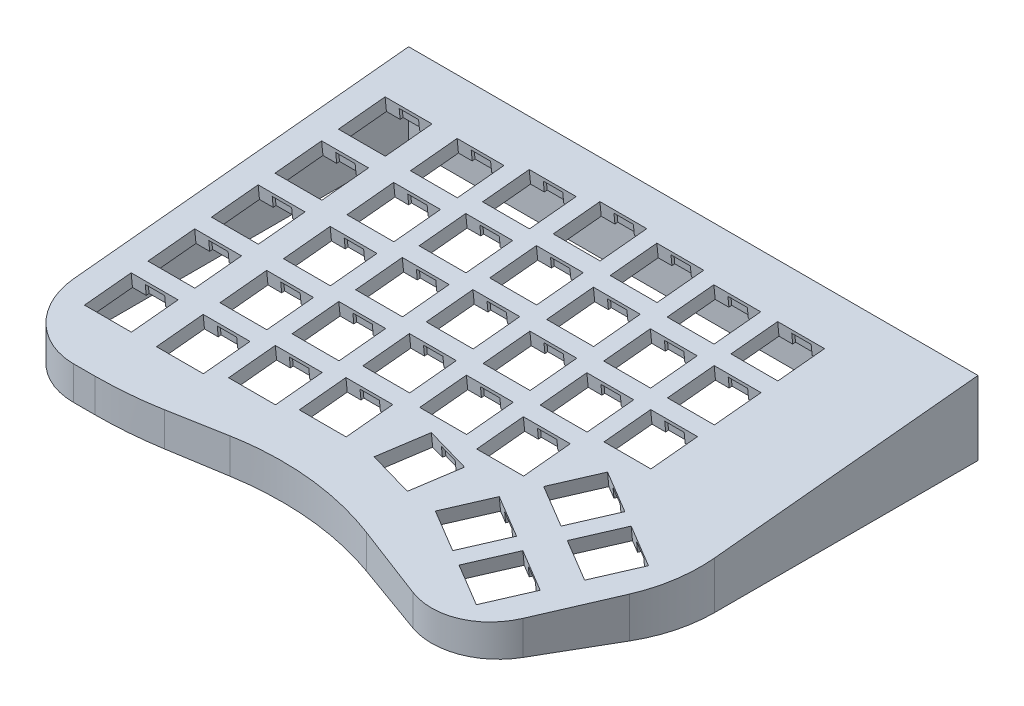
SolidWorks part; units mm, degrees
ref_plane "Front Plane" through (0, 0, 0) normal (0, 0, 1) x (1, 0, 0)
ref_plane "Top Plane" through (0, 0, 0) normal (0, 1, 0) x (1, 0, 0)
ref_plane "Right Plane" through (0, 0, 0) normal (1, 0, 0) x (0, 0, -1)
sketch "Key Template" plane through (0, 0, 0) normal (0, 1, 0) x (1, 0, 0)
  line L0 (41.2542, 10.7029) -> (27.2527, 10.7029)
  line L1 (27.2527, 10.7029) -> (27.2527, 9.7037)
  line L2 (27.2527, 9.7037) -> (26.4536, 9.7037)
  line L3 (26.4536, 9.7037) -> (26.4536, 6.6027)
  line L4 (26.4536, 6.6027) -> (27.2527, 6.6027)
  line L5 (27.2527, 6.6027) -> (27.2527, 0.8025)
  line L6 (27.2527, 0.8025) -> (26.4536, 0.8025)
  line L7 (26.4536, 0.8025) -> (26.4536, -2.2968)
  line L8 (26.4536, -2.2968) -> (27.2527, -2.2968)
  line L9 (27.2527, -2.2968) -> (27.2527, -3.2974)
  line L10 (27.2527, -3.2974) -> (41.2542, -3.2974)
  line L11 (41.2542, -3.2974) -> (41.2542, -2.2968)
  line L12 (41.2542, -2.2968) -> (42.0532, -2.2968)
  line L13 (42.0532, -2.2968) -> (42.0532, 0.8025)
  line L14 (42.0532, 0.8025) -> (41.2542, 0.8025)
  line L15 (41.2542, 0.8025) -> (41.2542, 6.6027)
  line L16 (41.2542, 6.6027) -> (42.0532, 6.6027)
  line L17 (42.0532, 6.6027) -> (42.0532, 9.7037)
  line L18 (42.0532, 9.7037) -> (41.2542, 9.7037)
  line L19 (41.2542, 9.7037) -> (41.2542, 10.7029)
  line L20 (41.2542, 29.7536) -> (27.2527, 29.7536)
  line L21 (27.2527, 29.7536) -> (27.2527, 28.7545)
  line L22 (27.2527, 28.7545) -> (26.4536, 28.7545)
  line L23 (26.4536, 28.7545) -> (26.4536, 25.6534)
  line L24 (26.4536, 25.6534) -> (27.2527, 25.6534)
  line L25 (27.2527, 25.6534) -> (27.2527, 19.8532)
  line L26 (27.2527, 19.8532) -> (26.4536, 19.8532)
  line L27 (26.4536, 19.8532) -> (26.4536, 16.7539)
  line L28 (26.4536, 16.7539) -> (27.2527, 16.7539)
  line L29 (27.2527, 16.7539) -> (27.2527, 15.7534)
  line L30 (27.2527, 15.7534) -> (41.2542, 15.7534)
  line L31 (41.2542, 15.7534) -> (41.2542, 16.7539)
  line L32 (41.2542, 16.7539) -> (42.0532, 16.7539)
  line L33 (42.0532, 16.7539) -> (42.0532, 19.8532)
  line L34 (42.0532, 19.8532) -> (41.2542, 19.8532)
  line L35 (41.2542, 19.8532) -> (41.2542, 25.6534)
  line L36 (41.2542, 25.6534) -> (42.0532, 25.6534)
  line L37 (42.0532, 25.6534) -> (42.0532, 28.7545)
  line L38 (42.0532, 28.7545) -> (41.2542, 28.7545)
  line L39 (41.2542, 28.7545) -> (41.2542, 29.7536)
  line L40 (27.2527, 53.8544) -> (41.2542, 53.8544)
  line L41 (41.2542, 53.8544) -> (41.2542, 54.8554)
  line L42 (41.2542, 54.8554) -> (42.0532, 54.8554)
  line L43 (42.0532, 54.8554) -> (42.0532, 57.9546)
  line L44 (42.0532, 57.9546) -> (41.2542, 57.9546)
  line L45 (41.2542, 57.9546) -> (41.2542, 63.7548)
  line L46 (41.2542, 63.7548) -> (42.0532, 63.7548)
  line L47 (42.0532, 63.7548) -> (42.0532, 66.8559)
  line L48 (42.0532, 66.8559) -> (41.2542, 66.8559)
  line L49 (41.2542, 66.8559) -> (41.2542, 67.8549)
  line L50 (41.2542, 67.8549) -> (27.2527, 67.8549)
  line L51 (27.2527, 67.8549) -> (27.2527, 66.8559)
  line L52 (27.2527, 66.8559) -> (26.4536, 66.8559)
  line L53 (26.4536, 66.8559) -> (26.4536, 63.7548)
  line L54 (26.4536, 63.7548) -> (27.2527, 63.7548)
  line L55 (27.2527, 63.7548) -> (27.2527, 57.9546)
  line L56 (27.2527, 57.9546) -> (26.4536, 57.9546)
  line L57 (26.4536, 57.9546) -> (26.4536, 54.8554)
  line L58 (26.4536, 54.8554) -> (27.2527, 54.8554)
  line L59 (27.2527, 54.8554) -> (27.2527, 53.8544)
  line L60 (27.2527, 34.8041) -> (41.2542, 34.8041)
  line L61 (41.2542, 34.8041) -> (41.2542, 35.8046)
  line L62 (41.2542, 35.8046) -> (42.0532, 35.8046)
  line L63 (42.0532, 35.8046) -> (42.0532, 38.9039)
  line L64 (42.0532, 38.9039) -> (41.2542, 38.9039)
  line L65 (41.2542, 38.9039) -> (41.2542, 44.7042)
  line L66 (41.2542, 44.7042) -> (42.0532, 44.7042)
  line L67 (42.0532, 44.7042) -> (42.0532, 47.8052)
  line L68 (42.0532, 47.8052) -> (41.2542, 47.8052)
  line L69 (41.2542, 47.8052) -> (41.2542, 48.8043)
  line L70 (41.2542, 48.8043) -> (27.2527, 48.8043)
  line L71 (27.2527, 48.8043) -> (27.2527, 47.8052)
  line L72 (27.2527, 47.8052) -> (26.4536, 47.8052)
  line L73 (26.4536, 47.8052) -> (26.4536, 44.7042)
  line L74 (26.4536, 44.7042) -> (27.2527, 44.7042)
  line L75 (27.2527, 44.7042) -> (27.2527, 38.9039)
  line L76 (27.2527, 38.9039) -> (26.4536, 38.9039)
  line L77 (26.4536, 38.9039) -> (26.4536, 35.8046)
  line L78 (26.4536, 35.8046) -> (27.2527, 35.8046)
  line L79 (27.2527, 35.8046) -> (27.2527, 34.8041)
  line L80 (46.3034, 44.3295) -> (60.3049, 44.3295)
  line L81 (60.3049, 44.3295) -> (60.3049, 45.33)
  line L82 (60.3049, 45.33) -> (61.1039, 45.33)
  line L83 (61.1039, 45.33) -> (61.1039, 48.4293)
  line L84 (61.1039, 48.4293) -> (60.3049, 48.4293)
  line L85 (60.3049, 48.4293) -> (60.3049, 54.2294)
  line L86 (60.3049, 54.2294) -> (61.1039, 54.2294)
  line L87 (61.1039, 54.2294) -> (61.1039, 57.3305)
  line L88 (61.1039, 57.3305) -> (60.3049, 57.3305)
  line L89 (60.3049, 57.3305) -> (60.3049, 58.3296)
  line L90 (60.3049, 58.3296) -> (46.3034, 58.3296)
  line L91 (46.3034, 58.3296) -> (46.3034, 57.3305)
  line L92 (46.3034, 57.3305) -> (45.5034, 57.3305)
  line L93 (45.5034, 57.3305) -> (45.5034, 54.2294)
  line L94 (45.5034, 54.2294) -> (46.3034, 54.2294)
  line L95 (46.3034, 54.2294) -> (46.3034, 48.4293)
  line L96 (46.3034, 48.4293) -> (45.5034, 48.4293)
  line L97 (45.5034, 48.4293) -> (45.5034, 45.33)
  line L98 (45.5034, 45.33) -> (46.3034, 45.33)
  line L99 (46.3034, 45.33) -> (46.3034, 44.3295)
  line L100 (60.3043, 34.5169) -> (46.304, 34.5169)
  line L101 (46.304, 34.5169) -> (46.304, 33.5169)
  line L102 (46.304, 33.5169) -> (45.505, 33.5169)
  line L103 (45.505, 33.5169) -> (45.505, 30.4158)
  line L104 (45.505, 30.4158) -> (46.304, 30.4158)
  line L105 (46.304, 30.4158) -> (46.304, 24.6166)
  line L106 (46.304, 24.6166) -> (45.505, 24.6166)
  line L107 (45.505, 24.6166) -> (45.505, 21.5164)
  line L108 (45.505, 21.5164) -> (46.304, 21.5164)
  line L109 (46.304, 21.5164) -> (46.304, 20.5154)
  line L110 (46.304, 20.5154) -> (60.3043, 20.5154)
  line L111 (60.3043, 20.5154) -> (60.3043, 21.5164)
  line L112 (60.3043, 21.5164) -> (61.1051, 21.5164)
  line L113 (61.1051, 21.5164) -> (61.1051, 24.6166)
  line L114 (61.1051, 24.6166) -> (60.3043, 24.6166)
  line L115 (60.3043, 24.6166) -> (60.3043, 30.4158)
  line L116 (60.3043, 30.4158) -> (61.1051, 30.4158)
  line L117 (61.1051, 30.4158) -> (61.1051, 33.5169)
  line L118 (61.1051, 33.5169) -> (60.3043, 33.5169)
  line L119 (60.3043, 33.5169) -> (60.3043, 34.5169)
  line L120 (63.726, -14.424) -> (75.8515, -21.4247)
  line L121 (75.8515, -21.4247) -> (76.3515, -20.5579)
  line L122 (76.3515, -20.5579) -> (77.0445, -20.9575)
  line L123 (77.0445, -20.9575) -> (78.5936, -18.273)
  line L124 (78.5936, -18.273) -> (77.9016, -17.8734)
  line L125 (77.9016, -17.8734) -> (80.8017, -12.8502)
  line L126 (80.8017, -12.8502) -> (81.4947, -13.2499)
  line L127 (81.4947, -13.2499) -> (83.0448, -10.5655)
  line L128 (83.0448, -10.5655) -> (82.3517, -10.1644)
  line L129 (82.3517, -10.1644) -> (82.8518, -9.299)
  line L130 (82.8518, -9.299) -> (70.7263, -2.2982)
  line L131 (70.7263, -2.2982) -> (70.2253, -3.165)
  line L132 (70.2253, -3.165) -> (69.5343, -2.7639)
  line L133 (69.5343, -2.7639) -> (67.9842, -5.45)
  line L134 (67.9842, -5.45) -> (68.6752, -5.8493)
  line L135 (68.6752, -5.8493) -> (65.7761, -10.8727)
  line L136 (65.7761, -10.8727) -> (65.0841, -10.4731)
  line L137 (65.0841, -10.4731) -> (63.534, -13.1574)
  line L138 (63.534, -13.1574) -> (64.2261, -13.5571)
  line L139 (64.2261, -13.5571) -> (63.726, -14.424)
  line L140 (58.8189, -22.9227) -> (51.8186, -35.0472)
  line L141 (51.8186, -35.0472) -> (52.6856, -35.546)
  line L142 (52.6856, -35.546) -> (52.2856, -36.2392)
  line L143 (52.2856, -36.2392) -> (54.9707, -37.7896)
  line L144 (54.9707, -37.7896) -> (55.3697, -37.0963)
  line L145 (55.3697, -37.0963) -> (60.3929, -39.9973)
  line L146 (60.3929, -39.9973) -> (59.9939, -40.6904)
  line L147 (59.9939, -40.6904) -> (62.678, -42.2394)
  line L148 (62.678, -42.2394) -> (63.079, -41.5462)
  line L149 (63.079, -41.5462) -> (63.9451, -42.0465)
  line L150 (63.9451, -42.0465) -> (70.9453, -29.9221)
  line L151 (70.9453, -29.9221) -> (70.0783, -29.4217)
  line L152 (70.0783, -29.4217) -> (70.4793, -28.73)
  line L153 (70.4793, -28.73) -> (67.7932, -27.1797)
  line L154 (67.7932, -27.1797) -> (67.3942, -27.8728)
  line L155 (67.3942, -27.8728) -> (62.371, -24.9719)
  line L156 (62.371, -24.9719) -> (62.771, -24.2787)
  line L157 (62.771, -24.2787) -> (60.0859, -22.7298)
  line L158 (60.0859, -22.7298) -> (59.6859, -23.4216)
  line L159 (59.6859, -23.4216) -> (58.8189, -22.9227)
  line L160 (42.3212, -13.3973) -> (35.32, -25.5218)
  line L161 (35.32, -25.5218) -> (36.187, -26.0206)
  line L162 (36.187, -26.0206) -> (35.786, -26.7138)
  line L163 (35.786, -26.7138) -> (38.4721, -28.2642)
  line L164 (38.4721, -28.2642) -> (38.8711, -27.571)
  line L165 (38.8711, -27.571) -> (43.8953, -30.4719)
  line L166 (43.8953, -30.4719) -> (43.4953, -31.165)
  line L167 (43.4953, -31.165) -> (46.1794, -32.7141)
  line L168 (46.1794, -32.7141) -> (46.5804, -32.0208)
  line L169 (46.5804, -32.0208) -> (47.4464, -32.5212)
  line L170 (47.4464, -32.5212) -> (54.4467, -20.3967)
  line L171 (54.4467, -20.3967) -> (53.5797, -19.8964)
  line L172 (53.5797, -19.8964) -> (53.9807, -19.2047)
  line L173 (53.9807, -19.2047) -> (51.2946, -17.6542)
  line L174 (51.2946, -17.6542) -> (50.8956, -18.3474)
  line L175 (50.8956, -18.3474) -> (45.8724, -15.4465)
  line L176 (45.8724, -15.4465) -> (46.2724, -14.7534)
  line L177 (46.2724, -14.7534) -> (43.5873, -13.2044)
  line L178 (43.5873, -13.2044) -> (43.1863, -13.8963)
  line L179 (43.1863, -13.8963) -> (42.3212, -13.3973)
  line L180 (47.2284, -4.8986) -> (59.3529, -11.8994)
  line L181 (59.3529, -11.8994) -> (59.8529, -11.0326)
  line L182 (59.8529, -11.0326) -> (60.5459, -11.4324)
  line L183 (60.5459, -11.4324) -> (62.095, -8.7476)
  line L184 (62.095, -8.7476) -> (61.402, -8.3478)
  line L185 (61.402, -8.3478) -> (64.3031, -3.3249)
  line L186 (64.3031, -3.3249) -> (64.9961, -3.7246)
  line L187 (64.9961, -3.7246) -> (66.5461, -1.0402)
  line L188 (66.5461, -1.0402) -> (65.8531, -0.6391)
  line L189 (65.8531, -0.6391) -> (66.3531, 0.2264)
  line L190 (66.3531, 0.2264) -> (54.2287, 7.2271)
  line L191 (54.2287, 7.2271) -> (53.7287, 6.3603)
  line L192 (53.7287, 6.3603) -> (53.0356, 6.7614)
  line L193 (53.0356, 6.7614) -> (51.4856, 4.0753)
  line L194 (51.4856, 4.0753) -> (52.1786, 3.676)
  line L195 (52.1786, 3.676) -> (49.2775, -1.3474)
  line L196 (49.2775, -1.3474) -> (48.5855, -0.9478)
  line L197 (48.5855, -0.9478) -> (47.0354, -3.6321)
  line L198 (47.0354, -3.6321) -> (47.7284, -4.0318)
  line L199 (47.7284, -4.0318) -> (47.2284, -4.8986)
  line L200 (-15.898, -5.9666) -> (-29.8992, -5.9666)
  line L201 (-29.8992, -5.9666) -> (-29.8992, -6.967)
  line L202 (-29.8992, -6.967) -> (-30.6986, -6.967)
  line L203 (-30.6986, -6.967) -> (-30.6986, -10.0667)
  line L204 (-30.6986, -10.0667) -> (-29.8992, -10.0667)
  line L205 (-29.8992, -10.0667) -> (-29.8992, -15.8668)
  line L206 (-29.8992, -15.8668) -> (-30.6986, -15.8668)
  line L207 (-30.6986, -15.8668) -> (-30.6986, -18.9675)
  line L208 (-30.6986, -18.9675) -> (-29.8992, -18.9675)
  line L209 (-29.8992, -18.9675) -> (-29.8992, -19.9667)
  line L210 (-29.8992, -19.9667) -> (-15.898, -19.9667)
  line L211 (-15.898, -19.9667) -> (-15.898, -18.9675)
  line L212 (-15.898, -18.9675) -> (-15.0985, -18.9675)
  line L213 (-15.0985, -18.9675) -> (-15.0985, -15.8668)
  line L214 (-15.0985, -15.8668) -> (-15.898, -15.8668)
  line L215 (-15.898, -15.8668) -> (-15.898, -10.0667)
  line L216 (-15.898, -10.0667) -> (-15.0985, -10.0667)
  line L217 (-15.0985, -10.0667) -> (-15.0985, -6.967)
  line L218 (-15.0985, -6.967) -> (-15.898, -6.967)
  line L219 (-15.898, -6.967) -> (-15.898, -5.9666)
  line L220 (3.1527, -3.5852) -> (-10.8485, -3.5852)
  line L221 (-10.8485, -3.5852) -> (-10.8485, -4.5857)
  line L222 (-10.8485, -4.5857) -> (-11.6479, -4.5857)
  line L223 (-11.6479, -4.5857) -> (-11.6479, -7.6853)
  line L224 (-11.6479, -7.6853) -> (-10.8485, -7.6853)
  line L225 (-10.8485, -7.6853) -> (-10.8485, -13.4855)
  line L226 (-10.8485, -13.4855) -> (-11.6479, -13.4855)
  line L227 (-11.6479, -13.4855) -> (-11.6479, -16.5863)
  line L228 (-11.6479, -16.5863) -> (-10.8485, -16.5863)
  line L229 (-10.8485, -16.5863) -> (-10.8485, -17.5854)
  line L230 (-10.8485, -17.5854) -> (3.1527, -17.5854)
  line L231 (3.1527, -17.5854) -> (3.1527, -16.5863)
  line L232 (3.1527, -16.5863) -> (3.9522, -16.5863)
  line L233 (3.9522, -16.5863) -> (3.9522, -13.4855)
  line L234 (3.9522, -13.4855) -> (3.1527, -13.4855)
  line L235 (3.1527, -13.4855) -> (3.1527, -7.6853)
  line L236 (3.1527, -7.6853) -> (3.9522, -7.6853)
  line L237 (3.9522, -7.6853) -> (3.9522, -4.5857)
  line L238 (3.9522, -4.5857) -> (3.1527, -4.5857)
  line L239 (3.1527, -4.5857) -> (3.1527, -3.5852)
  line L240 (3.1527, 15.4656) -> (-10.8485, 15.4656)
  line L241 (-10.8485, 15.4656) -> (-10.8485, 14.465)
  line L242 (-10.8485, 14.465) -> (-11.6479, 14.465)
  line L243 (-11.6479, 14.465) -> (-11.6479, 11.3654)
  line L244 (-11.6479, 11.3654) -> (-10.8485, 11.3654)
  line L245 (-10.8485, 11.3654) -> (-10.8485, 5.5652)
  line L246 (-10.8485, 5.5652) -> (-11.6479, 5.5652)
  line L247 (-11.6479, 5.5652) -> (-11.6479, 2.4645)
  line L248 (-11.6479, 2.4645) -> (-10.8485, 2.4645)
  line L249 (-10.8485, 2.4645) -> (-10.8485, 1.4653)
  line L250 (-10.8485, 1.4653) -> (3.1527, 1.4653)
  line L251 (3.1527, 1.4653) -> (3.1527, 2.4645)
  line L252 (3.1527, 2.4645) -> (3.9522, 2.4645)
  line L253 (3.9522, 2.4645) -> (3.9522, 5.5652)
  line L254 (3.9522, 5.5652) -> (3.1527, 5.5652)
  line L255 (3.1527, 5.5652) -> (3.1527, 11.3654)
  line L256 (3.1527, 11.3654) -> (3.9522, 11.3654)
  line L257 (3.9522, 11.3654) -> (3.9522, 14.465)
  line L258 (3.9522, 14.465) -> (3.1527, 14.465)
  line L259 (3.1527, 14.465) -> (3.1527, 15.4656)
  line L260 (-15.898, 13.0842) -> (-29.8992, 13.0842)
  line L261 (-29.8992, 13.0842) -> (-29.8992, 12.0837)
  line L262 (-29.8992, 12.0837) -> (-30.6986, 12.0837)
  line L263 (-30.6986, 12.0837) -> (-30.6986, 8.984)
  line L264 (-30.6986, 8.984) -> (-29.8992, 8.984)
  line L265 (-29.8992, 8.984) -> (-29.8992, 3.1838)
  line L266 (-29.8992, 3.1838) -> (-30.6986, 3.1838)
  line L267 (-30.6986, 3.1838) -> (-30.6986, 0.0832)
  line L268 (-30.6986, 0.0832) -> (-29.8992, 0.0832)
  line L269 (-29.8992, 0.0832) -> (-29.8992, -0.916)
  line L270 (-29.8992, -0.916) -> (-15.898, -0.916)
  line L271 (-15.898, -0.916) -> (-15.898, 0.0832)
  line L272 (-15.898, 0.0832) -> (-15.0985, 0.0832)
  line L273 (-15.0985, 0.0832) -> (-15.0985, 3.1838)
  line L274 (-15.0985, 3.1838) -> (-15.898, 3.1838)
  line L275 (-15.898, 3.1838) -> (-15.898, 8.984)
  line L276 (-15.898, 8.984) -> (-15.0985, 8.984)
  line L277 (-15.0985, 8.984) -> (-15.0985, 12.0837)
  line L278 (-15.0985, 12.0837) -> (-15.898, 12.0837)
  line L279 (-15.898, 12.0837) -> (-15.898, 13.0842)
  line L280 (-29.8992, 18.1348) -> (-15.898, 18.1348)
  line L281 (-15.898, 18.1348) -> (-15.898, 19.1339)
  line L282 (-15.898, 19.1339) -> (-15.0985, 19.1339)
  line L283 (-15.0985, 19.1339) -> (-15.0985, 22.2345)
  line L284 (-15.0985, 22.2345) -> (-15.898, 22.2345)
  line L285 (-15.898, 22.2345) -> (-15.898, 28.0347)
  line L286 (-15.898, 28.0347) -> (-15.0985, 28.0347)
  line L287 (-15.0985, 28.0347) -> (-15.0985, 31.1345)
  line L288 (-15.0985, 31.1345) -> (-15.898, 31.1345)
  line L289 (-15.898, 31.1345) -> (-15.898, 32.1349)
  line L290 (-15.898, 32.1349) -> (-29.8992, 32.1349)
  line L291 (-29.8992, 32.1349) -> (-29.8992, 31.1345)
  line L292 (-29.8992, 31.1345) -> (-30.6986, 31.1345)
  line L293 (-30.6986, 31.1345) -> (-30.6986, 28.0347)
  line L294 (-30.6986, 28.0347) -> (-29.8992, 28.0347)
  line L295 (-29.8992, 28.0347) -> (-29.8992, 22.2345)
  line L296 (-29.8992, 22.2345) -> (-30.6986, 22.2345)
  line L297 (-30.6986, 22.2345) -> (-30.6986, 19.1339)
  line L298 (-30.6986, 19.1339) -> (-29.8992, 19.1339)
  line L299 (-29.8992, 19.1339) -> (-29.8992, 18.1348)
  line L300 (-48.9499, 13.3721) -> (-34.9501, 13.3721)
  line L301 (-34.9501, 13.3721) -> (-34.9501, 14.3726)
  line L302 (-34.9501, 14.3726) -> (-34.1493, 14.3726)
  line L303 (-34.1493, 14.3726) -> (-34.1493, 17.4718)
  line L304 (-34.1493, 17.4718) -> (-34.9501, 17.4718)
  line L305 (-34.9501, 17.4718) -> (-34.9501, 23.2721)
  line L306 (-34.9501, 23.2721) -> (-34.1493, 23.2721)
  line L307 (-34.1493, 23.2721) -> (-34.1493, 26.3732)
  line L308 (-34.1493, 26.3732) -> (-34.9501, 26.3732)
  line L309 (-34.9501, 26.3732) -> (-34.9501, 27.3722)
  line L310 (-34.9501, 27.3722) -> (-48.9499, 27.3722)
  line L311 (-48.9499, 27.3722) -> (-48.9499, 26.3732)
  line L312 (-48.9499, 26.3732) -> (-49.7493, 26.3732)
  line L313 (-49.7493, 26.3732) -> (-49.7493, 23.2721)
  line L314 (-49.7493, 23.2721) -> (-48.9499, 23.2721)
  line L315 (-48.9499, 23.2721) -> (-48.9499, 17.4718)
  line L316 (-48.9499, 17.4718) -> (-49.7493, 17.4718)
  line L317 (-49.7493, 17.4718) -> (-49.7493, 14.3726)
  line L318 (-49.7493, 14.3726) -> (-48.9499, 14.3726)
  line L319 (-48.9499, 14.3726) -> (-48.9499, 13.3721)
  line L320 (-48.9499, -5.6786) -> (-34.9501, -5.6786)
  line L321 (-34.9501, -5.6786) -> (-34.9501, -4.6781)
  line L322 (-34.9501, -4.6781) -> (-34.1493, -4.6781)
  line L323 (-34.1493, -4.6781) -> (-34.1493, -1.5789)
  line L324 (-34.1493, -1.5789) -> (-34.9501, -1.5789)
  line L325 (-34.9501, -1.5789) -> (-34.9501, 4.2213)
  line L326 (-34.9501, 4.2213) -> (-34.1493, 4.2213)
  line L327 (-34.1493, 4.2213) -> (-34.1493, 7.3224)
  line L328 (-34.1493, 7.3224) -> (-34.9501, 7.3224)
  line L329 (-34.9501, 7.3224) -> (-34.9501, 8.3215)
  line L330 (-34.9501, 8.3215) -> (-48.9499, 8.3215)
  line L331 (-48.9499, 8.3215) -> (-48.9499, 7.3224)
  line L332 (-48.9499, 7.3224) -> (-49.7493, 7.3224)
  line L333 (-49.7493, 7.3224) -> (-49.7493, 4.2213)
  line L334 (-49.7493, 4.2213) -> (-48.9499, 4.2213)
  line L335 (-48.9499, 4.2213) -> (-48.9499, -1.5789)
  line L336 (-48.9499, -1.5789) -> (-49.7493, -1.5789)
  line L337 (-49.7493, -1.5789) -> (-49.7493, -4.6781)
  line L338 (-49.7493, -4.6781) -> (-48.9499, -4.6781)
  line L339 (-48.9499, -4.6781) -> (-48.9499, -5.6786)
  line L340 (-34.9487, -10.7292) -> (-48.9499, -10.7292)
  line L341 (-48.9499, -10.7292) -> (-48.9499, -11.7283)
  line L342 (-48.9499, -11.7283) -> (-49.7493, -11.7283)
  line L343 (-49.7493, -11.7283) -> (-49.7493, -14.8292)
  line L344 (-49.7493, -14.8292) -> (-48.9499, -14.8292)
  line L345 (-48.9499, -14.8292) -> (-48.9499, -20.6295)
  line L346 (-48.9499, -20.6295) -> (-49.7493, -20.6295)
  line L347 (-49.7493, -20.6295) -> (-49.7493, -23.7289)
  line L348 (-49.7493, -23.7289) -> (-48.9499, -23.7289)
  line L349 (-48.9499, -23.7289) -> (-48.9499, -24.7294)
  line L350 (-48.9499, -24.7294) -> (-34.9487, -24.7294)
  line L351 (-34.9487, -24.7294) -> (-34.9487, -23.7289)
  line L352 (-34.9487, -23.7289) -> (-34.1493, -23.7289)
  line L353 (-34.1493, -23.7289) -> (-34.1493, -20.6295)
  line L354 (-34.1493, -20.6295) -> (-34.9487, -20.6295)
  line L355 (-34.9487, -20.6295) -> (-34.9487, -14.8292)
  line L356 (-34.9487, -14.8292) -> (-34.1493, -14.8292)
  line L357 (-34.1493, -14.8292) -> (-34.1493, -11.7283)
  line L358 (-34.1493, -11.7283) -> (-34.9487, -11.7283)
  line L359 (-34.9487, -11.7283) -> (-34.9487, -10.7292)
  line L360 (-53.9993, -10.7292) -> (-68.0006, -10.7292)
  line L361 (-68.0006, -10.7292) -> (-68.0006, -11.7283)
  line L362 (-68.0006, -11.7283) -> (-68.8, -11.7283)
  line L363 (-68.8, -11.7283) -> (-68.8, -14.8292)
  line L364 (-68.8, -14.8292) -> (-68.0006, -14.8292)
  line L365 (-68.0006, -14.8292) -> (-68.0006, -20.6295)
  line L366 (-68.0006, -20.6295) -> (-68.8, -20.6295)
  line L367 (-68.8, -20.6295) -> (-68.8, -23.7289)
  line L368 (-68.8, -23.7289) -> (-68.0006, -23.7289)
  line L369 (-68.0006, -23.7289) -> (-68.0006, -24.7294)
  line L370 (-68.0006, -24.7294) -> (-53.9993, -24.7294)
  line L371 (-53.9993, -24.7294) -> (-53.9993, -23.7289)
  line L372 (-53.9993, -23.7289) -> (-53.2, -23.7289)
  line L373 (-53.2, -23.7289) -> (-53.2, -20.6295)
  line L374 (-53.2, -20.6295) -> (-53.9993, -20.6295)
  line L375 (-53.9993, -20.6295) -> (-53.9993, -14.8292)
  line L376 (-53.9993, -14.8292) -> (-53.2, -14.8292)
  line L377 (-53.2, -14.8292) -> (-53.2, -11.7283)
  line L378 (-53.2, -11.7283) -> (-53.9993, -11.7283)
  line L379 (-53.9993, -11.7283) -> (-53.9993, -10.7292)
  line L380 (-56.382, 8.3215) -> (-70.382, 8.3215)
  line L381 (-70.382, 8.3215) -> (-70.382, 7.3224)
  line L382 (-70.382, 7.3224) -> (-71.1827, 7.3224)
  line L383 (-71.1827, 7.3224) -> (-71.1827, 4.2213)
  line L384 (-71.1827, 4.2213) -> (-70.382, 4.2213)
  line L385 (-70.382, 4.2213) -> (-70.382, -1.5789)
  line L386 (-70.382, -1.5789) -> (-71.1827, -1.5789)
  line L387 (-71.1827, -1.5789) -> (-71.1827, -4.6781)
  line L388 (-71.1827, -4.6781) -> (-70.382, -4.6781)
  line L389 (-70.382, -4.6781) -> (-70.382, -5.6786)
  line L390 (-70.382, -5.6786) -> (-56.382, -5.6786)
  line L391 (-56.382, -5.6786) -> (-56.382, -4.6781)
  line L392 (-56.382, -4.6781) -> (-55.5813, -4.6781)
  line L393 (-55.5813, -4.6781) -> (-55.5813, -1.5789)
  line L394 (-55.5813, -1.5789) -> (-56.382, -1.5789)
  line L395 (-56.382, -1.5789) -> (-56.382, 4.2213)
  line L396 (-56.382, 4.2213) -> (-55.5813, 4.2213)
  line L397 (-55.5813, 4.2213) -> (-55.5813, 7.3224)
  line L398 (-55.5813, 7.3224) -> (-56.382, 7.3224)
  line L399 (-56.382, 7.3224) -> (-56.382, 8.3215)
  line L400 (-56.382, 27.3722) -> (-70.382, 27.3722)
  line L401 (-70.382, 27.3722) -> (-70.382, 26.3732)
  line L402 (-70.382, 26.3732) -> (-71.1827, 26.3732)
  line L403 (-71.1827, 26.3732) -> (-71.1827, 23.2721)
  line L404 (-71.1827, 23.2721) -> (-70.382, 23.2721)
  line L405 (-70.382, 23.2721) -> (-70.382, 17.4718)
  line L406 (-70.382, 17.4718) -> (-71.1827, 17.4718)
  line L407 (-71.1827, 17.4718) -> (-71.1827, 14.3726)
  line L408 (-71.1827, 14.3726) -> (-70.382, 14.3726)
  line L409 (-70.382, 14.3726) -> (-70.382, 13.3721)
  line L410 (-70.382, 13.3721) -> (-56.382, 13.3721)
  line L411 (-56.382, 13.3721) -> (-56.382, 14.3726)
  line L412 (-56.382, 14.3726) -> (-55.5813, 14.3726)
  line L413 (-55.5813, 14.3726) -> (-55.5813, 17.4718)
  line L414 (-55.5813, 17.4718) -> (-56.382, 17.4718)
  line L415 (-56.382, 17.4718) -> (-56.382, 23.2721)
  line L416 (-56.382, 23.2721) -> (-55.5813, 23.2721)
  line L417 (-55.5813, 23.2721) -> (-55.5813, 26.3732)
  line L418 (-55.5813, 26.3732) -> (-56.382, 26.3732)
  line L419 (-56.382, 26.3732) -> (-56.382, 27.3722)
  line L420 (3.1527, 34.5163) -> (-10.8485, 34.5163)
  line L421 (-10.8485, 34.5163) -> (-10.8485, 33.5157)
  line L422 (-10.8485, 33.5157) -> (-11.6479, 33.5157)
  line L423 (-11.6479, 33.5157) -> (-11.6479, 30.4161)
  line L424 (-11.6479, 30.4161) -> (-10.8485, 30.4161)
  line L425 (-10.8485, 30.4161) -> (-10.8485, 24.6159)
  line L426 (-10.8485, 24.6159) -> (-11.6479, 24.6159)
  line L427 (-11.6479, 24.6159) -> (-11.6479, 21.5152)
  line L428 (-11.6479, 21.5152) -> (-10.8485, 21.5152)
  line L429 (-10.8485, 21.5152) -> (-10.8485, 20.516)
  line L430 (-10.8485, 20.516) -> (3.1527, 20.516)
  line L431 (3.1527, 20.516) -> (3.1527, 21.5152)
  line L432 (3.1527, 21.5152) -> (3.9522, 21.5152)
  line L433 (3.9522, 21.5152) -> (3.9522, 24.6159)
  line L434 (3.9522, 24.6159) -> (3.1527, 24.6159)
  line L435 (3.1527, 24.6159) -> (3.1527, 30.4161)
  line L436 (3.1527, 30.4161) -> (3.9522, 30.4161)
  line L437 (3.9522, 30.4161) -> (3.9522, 33.5157)
  line L438 (3.9522, 33.5157) -> (3.1527, 33.5157)
  line L439 (3.1527, 33.5157) -> (3.1527, 34.5163)
  line L440 (3.1527, 53.5674) -> (-10.8485, 53.5674)
  line L441 (-10.8485, 53.5674) -> (-10.8485, 52.5664)
  line L442 (-10.8485, 52.5664) -> (-11.6479, 52.5664)
  line L443 (-11.6479, 52.5664) -> (-11.6479, 49.4668)
  line L444 (-11.6479, 49.4668) -> (-10.8485, 49.4668)
  line L445 (-10.8485, 49.4668) -> (-10.8485, 43.6666)
  line L446 (-10.8485, 43.6666) -> (-11.6479, 43.6666)
  line L447 (-11.6479, 43.6666) -> (-11.6479, 40.5659)
  line L448 (-11.6479, 40.5659) -> (-10.8485, 40.5659)
  line L449 (-10.8485, 40.5659) -> (-10.8485, 39.5668)
  line L450 (-10.8485, 39.5668) -> (3.1527, 39.5668)
  line L451 (3.1527, 39.5668) -> (3.1527, 40.5659)
  line L452 (3.1527, 40.5659) -> (3.9522, 40.5659)
  line L453 (3.9522, 40.5659) -> (3.9522, 43.6666)
  line L454 (3.9522, 43.6666) -> (3.1527, 43.6666)
  line L455 (3.1527, 43.6666) -> (3.1527, 49.4668)
  line L456 (3.1527, 49.4668) -> (3.9522, 49.4668)
  line L457 (3.9522, 49.4668) -> (3.9522, 52.5664)
  line L458 (3.9522, 52.5664) -> (3.1527, 52.5664)
  line L459 (3.1527, 52.5664) -> (3.1527, 53.5674)
  line L460 (-15.898, 51.1853) -> (-29.8992, 51.1853)
  line L461 (-29.8992, 51.1853) -> (-29.8992, 50.1852)
  line L462 (-29.8992, 50.1852) -> (-30.6986, 50.1852)
  line L463 (-30.6986, 50.1852) -> (-30.6986, 47.0856)
  line L464 (-30.6986, 47.0856) -> (-29.8992, 47.0856)
  line L465 (-29.8992, 47.0856) -> (-29.8992, 41.2852)
  line L466 (-29.8992, 41.2852) -> (-30.6986, 41.2852)
  line L467 (-30.6986, 41.2852) -> (-30.6986, 38.1846)
  line L468 (-30.6986, 38.1846) -> (-29.8992, 38.1846)
  line L469 (-29.8992, 38.1846) -> (-29.8992, 37.1855)
  line L470 (-29.8992, 37.1855) -> (-15.898, 37.1855)
  line L471 (-15.898, 37.1855) -> (-15.898, 38.1846)
  line L472 (-15.898, 38.1846) -> (-15.0985, 38.1846)
  line L473 (-15.0985, 38.1846) -> (-15.0985, 41.2852)
  line L474 (-15.0985, 41.2852) -> (-15.898, 41.2852)
  line L475 (-15.898, 41.2852) -> (-15.898, 47.0856)
  line L476 (-15.898, 47.0856) -> (-15.0985, 47.0856)
  line L477 (-15.0985, 47.0856) -> (-15.0985, 50.1852)
  line L478 (-15.0985, 50.1852) -> (-15.898, 50.1852)
  line L479 (-15.898, 50.1852) -> (-15.898, 51.1853)
  line L480 (-34.9501, 46.4229) -> (-48.9499, 46.4229)
  line L481 (-48.9499, 46.4229) -> (-48.9499, 45.4239)
  line L482 (-48.9499, 45.4239) -> (-49.7493, 45.4239)
  line L483 (-49.7493, 45.4239) -> (-49.7493, 42.3229)
  line L484 (-49.7493, 42.3229) -> (-48.9499, 42.3229)
  line L485 (-48.9499, 42.3229) -> (-48.9499, 36.5226)
  line L486 (-48.9499, 36.5226) -> (-49.7493, 36.5226)
  line L487 (-49.7493, 36.5226) -> (-49.7493, 33.4233)
  line L488 (-49.7493, 33.4233) -> (-48.9499, 33.4233)
  line L489 (-48.9499, 33.4233) -> (-48.9499, 32.4228)
  line L490 (-48.9499, 32.4228) -> (-34.9501, 32.4228)
  line L491 (-34.9501, 32.4228) -> (-34.9501, 33.4233)
  line L492 (-34.9501, 33.4233) -> (-34.1493, 33.4233)
  line L493 (-34.1493, 33.4233) -> (-34.1493, 36.5226)
  line L494 (-34.1493, 36.5226) -> (-34.9501, 36.5226)
  line L495 (-34.9501, 36.5226) -> (-34.9501, 42.3229)
  line L496 (-34.9501, 42.3229) -> (-34.1493, 42.3229)
  line L497 (-34.1493, 42.3229) -> (-34.1493, 45.4239)
  line L498 (-34.1493, 45.4239) -> (-34.9501, 45.4239)
  line L499 (-34.9501, 45.4239) -> (-34.9501, 46.4229)
  line L500 (-70.382, 51.4733) -> (-56.3813, 51.4733)
  line L501 (-56.3813, 51.4733) -> (-56.3813, 52.4744)
  line L502 (-56.3813, 52.4744) -> (-55.5813, 52.4744)
  line L503 (-55.5813, 52.4744) -> (-55.5813, 55.5744)
  line L504 (-55.5813, 55.5744) -> (-56.3813, 55.5744)
  line L505 (-56.3813, 55.5744) -> (-56.3813, 61.3744)
  line L506 (-56.3813, 61.3744) -> (-55.5813, 61.3744)
  line L507 (-55.5813, 61.3744) -> (-55.5813, 64.4744)
  line L508 (-55.5813, 64.4744) -> (-56.382, 64.4744)
  line L509 (-56.382, 64.4744) -> (-56.382, 65.4744)
  line L510 (-56.382, 65.4744) -> (-70.382, 65.4744)
  line L511 (-70.382, 65.4744) -> (-70.382, 64.4744)
  line L512 (-70.382, 64.4744) -> (-71.182, 64.4744)
  line L513 (-71.182, 64.4744) -> (-71.182, 61.3744)
  line L514 (-71.182, 61.3744) -> (-70.382, 61.3744)
  line L515 (-70.382, 61.3744) -> (-70.382, 55.5744)
  line L516 (-70.382, 55.5744) -> (-71.1827, 55.5744)
  line L517 (-71.1827, 55.5744) -> (-71.1827, 52.4744)
  line L518 (-71.1827, 52.4744) -> (-70.382, 52.4744)
  line L519 (-70.382, 52.4744) -> (-70.382, 51.4733)
  line L520 (-48.9499, 51.4733) -> (-34.9501, 51.4733)
  line L521 (-34.9501, 51.4733) -> (-34.9501, 52.4744)
  line L522 (-34.9501, 52.4744) -> (-34.1493, 52.4744)
  line L523 (-34.1493, 52.4744) -> (-34.1493, 55.5735)
  line L524 (-34.1493, 55.5735) -> (-34.9501, 55.5735)
  line L525 (-34.9501, 55.5735) -> (-34.9501, 61.3737)
  line L526 (-34.9501, 61.3737) -> (-34.1493, 61.3737)
  line L527 (-34.1493, 61.3737) -> (-34.1493, 64.4748)
  line L528 (-34.1493, 64.4748) -> (-34.9501, 64.4748)
  line L529 (-34.9501, 64.4748) -> (-34.9501, 65.4739)
  line L530 (-34.9501, 65.4739) -> (-48.9499, 65.4739)
  line L531 (-48.9499, 65.4739) -> (-48.9499, 64.4748)
  line L532 (-48.9499, 64.4748) -> (-49.7493, 64.4748)
  line L533 (-49.7493, 64.4748) -> (-49.7493, 61.3737)
  line L534 (-49.7493, 61.3737) -> (-48.9499, 61.3737)
  line L535 (-48.9499, 61.3737) -> (-48.9499, 55.5735)
  line L536 (-48.9499, 55.5735) -> (-49.7493, 55.5735)
  line L537 (-49.7493, 55.5735) -> (-49.7493, 52.4744)
  line L538 (-49.7493, 52.4744) -> (-48.9499, 52.4744)
  line L539 (-48.9499, 52.4744) -> (-48.9499, 51.4733)
  line L540 (-29.8992, 56.2365) -> (-15.898, 56.2365)
  line L541 (-15.898, 56.2365) -> (-15.898, 57.2355)
  line L542 (-15.898, 57.2355) -> (-15.0985, 57.2355)
  line L543 (-15.0985, 57.2355) -> (-15.0985, 60.3357)
  line L544 (-15.0985, 60.3357) -> (-15.898, 60.3357)
  line L545 (-15.898, 60.3357) -> (-15.898, 66.1359)
  line L546 (-15.898, 66.1359) -> (-15.0985, 66.1359)
  line L547 (-15.0985, 66.1359) -> (-15.0985, 69.236)
  line L548 (-15.0985, 69.236) -> (-15.898, 69.236)
  line L549 (-15.898, 69.236) -> (-15.898, 70.236)
  line L550 (-15.898, 70.236) -> (-29.8992, 70.236)
  line L551 (-29.8992, 70.236) -> (-29.8992, 69.236)
  line L552 (-29.8992, 69.236) -> (-30.6986, 69.236)
  line L553 (-30.6986, 69.236) -> (-30.6986, 66.1359)
  line L554 (-30.6986, 66.1359) -> (-29.8992, 66.1359)
  line L555 (-29.8992, 66.1359) -> (-29.8992, 60.3357)
  line L556 (-29.8992, 60.3357) -> (-30.6986, 60.3357)
  line L557 (-30.6986, 60.3357) -> (-30.6986, 57.2355)
  line L558 (-30.6986, 57.2355) -> (-29.8992, 57.2355)
  line L559 (-29.8992, 57.2355) -> (-29.8992, 56.2365)
  line L560 (-10.8485, 58.6176) -> (3.1527, 58.6176)
  line L561 (3.1527, 58.6176) -> (3.1527, 59.6166)
  line L562 (3.1527, 59.6166) -> (3.9522, 59.6166)
  line L563 (3.9522, 59.6166) -> (3.9522, 62.7177)
  line L564 (3.9522, 62.7177) -> (3.1527, 62.7177)
  line L565 (3.1527, 62.7177) -> (3.1527, 68.518)
  line L566 (3.1527, 68.518) -> (3.9522, 68.518)
  line L567 (3.9522, 68.518) -> (3.9522, 71.6171)
  line L568 (3.9522, 71.6171) -> (3.1527, 71.6171)
  line L569 (3.1527, 71.6171) -> (3.1527, 72.6181)
  line L570 (3.1527, 72.6181) -> (-10.8485, 72.6181)
  line L571 (-10.8485, 72.6181) -> (-10.8485, 71.6171)
  line L572 (-10.8485, 71.6171) -> (-11.6479, 71.6171)
  line L573 (-11.6479, 71.6171) -> (-11.6479, 68.518)
  line L574 (-11.6479, 68.518) -> (-10.8485, 68.518)
  line L575 (-10.8485, 68.518) -> (-10.8485, 62.7177)
  line L576 (-10.8485, 62.7177) -> (-11.6479, 62.7177)
  line L577 (-11.6479, 62.7177) -> (-11.6479, 59.6166)
  line L578 (-11.6479, 59.6166) -> (-10.8485, 59.6166)
  line L579 (-10.8485, 59.6166) -> (-10.8485, 58.6176)
  line L580 (8.2022, 56.2365) -> (22.2035, 56.2365)
  line L581 (22.2035, 56.2365) -> (22.2035, 57.2355)
  line L582 (22.2035, 57.2355) -> (23.0025, 57.2355)
  line L583 (23.0025, 57.2355) -> (23.0025, 60.3357)
  line L584 (23.0025, 60.3357) -> (22.2035, 60.3357)
  line L585 (22.2035, 60.3357) -> (22.2035, 66.1359)
  line L586 (22.2035, 66.1359) -> (23.0025, 66.1359)
  line L587 (23.0025, 66.1359) -> (23.0025, 69.236)
  line L588 (23.0025, 69.236) -> (22.2035, 69.236)
  line L589 (22.2035, 69.236) -> (22.2035, 70.236)
  line L590 (22.2035, 70.236) -> (8.2022, 70.236)
  line L591 (8.2022, 70.236) -> (8.2022, 69.236)
  line L592 (8.2022, 69.236) -> (7.4028, 69.236)
  line L593 (7.4028, 69.236) -> (7.4028, 66.1359)
  line L594 (7.4028, 66.1359) -> (8.2022, 66.1359)
  line L595 (8.2022, 66.1359) -> (8.2022, 60.3357)
  line L596 (8.2022, 60.3357) -> (7.4028, 60.3357)
  line L597 (7.4028, 60.3357) -> (7.4028, 57.2355)
  line L598 (7.4028, 57.2355) -> (8.2022, 57.2355)
  line L599 (8.2022, 57.2355) -> (8.2022, 56.2365)
  line L600 (8.2022, 37.1855) -> (22.2035, 37.1855)
  line L601 (22.2035, 37.1855) -> (22.2035, 38.1846)
  line L602 (22.2035, 38.1846) -> (23.0025, 38.1846)
  line L603 (23.0025, 38.1846) -> (23.0025, 41.2852)
  line L604 (23.0025, 41.2852) -> (22.2035, 41.2852)
  line L605 (22.2035, 41.2852) -> (22.2035, 47.0856)
  line L606 (22.2035, 47.0856) -> (23.0025, 47.0856)
  line L607 (23.0025, 47.0856) -> (23.0025, 50.1852)
  line L608 (23.0025, 50.1852) -> (22.2035, 50.1852)
  line L609 (22.2035, 50.1852) -> (22.2035, 51.1853)
  line L610 (22.2035, 51.1853) -> (8.2022, 51.1853)
  line L611 (8.2022, 51.1853) -> (8.2022, 50.1852)
  line L612 (8.2022, 50.1852) -> (7.4028, 50.1852)
  line L613 (7.4028, 50.1852) -> (7.4028, 47.0856)
  line L614 (7.4028, 47.0856) -> (8.2022, 47.0856)
  line L615 (8.2022, 47.0856) -> (8.2022, 41.2852)
  line L616 (8.2022, 41.2852) -> (7.4028, 41.2852)
  line L617 (7.4028, 41.2852) -> (7.4028, 38.1846)
  line L618 (7.4028, 38.1846) -> (8.2022, 38.1846)
  line L619 (8.2022, 38.1846) -> (8.2022, 37.1855)
  line L620 (22.2035, 13.0842) -> (8.2022, 13.0842)
  line L621 (8.2022, 13.0842) -> (8.2022, 12.0837)
  line L622 (8.2022, 12.0837) -> (7.4028, 12.0837)
  line L623 (7.4028, 12.0837) -> (7.4028, 8.984)
  line L624 (7.4028, 8.984) -> (8.2022, 8.984)
  line L625 (8.2022, 8.984) -> (8.2022, 3.1838)
  line L626 (8.2022, 3.1838) -> (7.4028, 3.1838)
  line L627 (7.4028, 3.1838) -> (7.4028, 0.0832)
  line L628 (7.4028, 0.0832) -> (8.2022, 0.0832)
  line L629 (8.2022, 0.0832) -> (8.2022, -0.916)
  line L630 (8.2022, -0.916) -> (22.2035, -0.916)
  line L631 (22.2035, -0.916) -> (22.2035, 0.0832)
  line L632 (22.2035, 0.0832) -> (23.0025, 0.0832)
  line L633 (23.0025, 0.0832) -> (23.0025, 3.1838)
  line L634 (23.0025, 3.1838) -> (22.2035, 3.1838)
  line L635 (22.2035, 3.1838) -> (22.2035, 8.984)
  line L636 (22.2035, 8.984) -> (23.0025, 8.984)
  line L637 (23.0025, 8.984) -> (23.0025, 12.0837)
  line L638 (23.0025, 12.0837) -> (22.2035, 12.0837)
  line L639 (22.2035, 12.0837) -> (22.2035, 13.0842)
  line L640 (8.2022, 18.1348) -> (22.2035, 18.1348)
  line L641 (22.2035, 18.1348) -> (22.2035, 19.1339)
  line L642 (22.2035, 19.1339) -> (23.0025, 19.1339)
  line L643 (23.0025, 19.1339) -> (23.0025, 22.2345)
  line L644 (23.0025, 22.2345) -> (22.2035, 22.2345)
  line L645 (22.2035, 22.2345) -> (22.2035, 28.0347)
  line L646 (22.2035, 28.0347) -> (23.0025, 28.0347)
  line L647 (23.0025, 28.0347) -> (23.0025, 31.1345)
  line L648 (23.0025, 31.1345) -> (22.2035, 31.1345)
  line L649 (22.2035, 31.1345) -> (22.2035, 32.1349)
  line L650 (22.2035, 32.1349) -> (8.2022, 32.1349)
  line L651 (8.2022, 32.1349) -> (8.2022, 31.1345)
  line L652 (8.2022, 31.1345) -> (7.4028, 31.1345)
  line L653 (7.4028, 31.1345) -> (7.4028, 28.0347)
  line L654 (7.4028, 28.0347) -> (8.2022, 28.0347)
  line L655 (8.2022, 28.0347) -> (8.2022, 22.2345)
  line L656 (8.2022, 22.2345) -> (7.4028, 22.2345)
  line L657 (7.4028, 22.2345) -> (7.4028, 19.1339)
  line L658 (7.4028, 19.1339) -> (8.2022, 19.1339)
  line L659 (8.2022, 19.1339) -> (8.2022, 18.1348)
  line L660 (12.6605, -21.0457) -> (26.1846, -24.6688)
  line L661 (26.1846, -24.6688) -> (26.4436, -23.7027)
  line L662 (26.4436, -23.7027) -> (27.2157, -23.9108)
  line L663 (27.2157, -23.9108) -> (28.0177, -20.9148)
  line L664 (28.0177, -20.9148) -> (27.2457, -20.7081)
  line L665 (27.2457, -20.7081) -> (28.7467, -15.1062)
  line L666 (28.7467, -15.1062) -> (29.5197, -15.3129)
  line L667 (29.5197, -15.3129) -> (30.3218, -12.3182)
  line L668 (30.3218, -12.3182) -> (29.5487, -12.1115)
  line L669 (29.5487, -12.1115) -> (29.8078, -11.1454)
  line L670 (29.8078, -11.1454) -> (16.2832, -7.5213)
  line L671 (16.2832, -7.5213) -> (16.0257, -8.4872)
  line L672 (16.0257, -8.4872) -> (15.2524, -8.2804)
  line L673 (15.2524, -8.2804) -> (14.4506, -11.275)
  line L674 (14.4506, -11.275) -> (15.2235, -11.4817)
  line L675 (15.2235, -11.4817) -> (13.7213, -17.0851)
  line L676 (13.7213, -17.0851) -> (12.9483, -16.8784)
  line L677 (12.9483, -16.8784) -> (12.1465, -19.8716)
  line L678 (12.1465, -19.8716) -> (12.9194, -20.0797)
  line L679 (12.9194, -20.0797) -> (12.6605, -21.0457)
  line L680 (-56.382, 46.4229) -> (-70.382, 46.4229)
  line L681 (-70.382, 46.4229) -> (-70.382, 45.4239)
  line L682 (-70.382, 45.4239) -> (-71.1827, 45.4239)
  line L683 (-71.1827, 45.4239) -> (-71.1827, 42.3229)
  line L684 (-71.1827, 42.3229) -> (-70.382, 42.3229)
  line L685 (-70.382, 42.3229) -> (-70.382, 36.5226)
  line L686 (-70.382, 36.5226) -> (-71.1827, 36.5226)
  line L687 (-71.1827, 36.5226) -> (-71.1827, 33.4233)
  line L688 (-71.1827, 33.4233) -> (-70.382, 33.4233)
  line L689 (-70.382, 33.4233) -> (-70.382, 32.4228)
  line L690 (-70.382, 32.4228) -> (-56.382, 32.4228)
  line L691 (-56.382, 32.4228) -> (-56.382, 33.4233)
  line L692 (-56.382, 33.4233) -> (-55.5813, 33.4233)
  line L693 (-55.5813, 33.4233) -> (-55.5813, 36.5226)
  line L694 (-55.5813, 36.5226) -> (-56.382, 36.5226)
  line L695 (-56.382, 36.5226) -> (-56.382, 42.3229)
  line L696 (-56.382, 42.3229) -> (-55.5813, 42.3229)
  line L697 (-55.5813, 42.3229) -> (-55.5813, 45.4239)
  line L698 (-55.5813, 45.4239) -> (-56.382, 45.4239)
  line L699 (-56.382, 45.4239) -> (-56.382, 46.4229)
  point P0 (51.2946, -17.6542)
  point P1 (22.2035, 8.984)
  point P2 (26.1846, -24.6688)
  point P3 (-70.382, 45.4239)
  dimension "D5" = 0.8
sketch "BodySketch" plane through (0, 0, 0) normal (0, 1, 0) x (1, 0, 0)
  line L0 (-78.182, 78.6181) -> (91.818, 78.6181)
  line L1 (91.818, 78.6181) -> (91.818, -10.7704)
  line L3 (91.818, -10.7704) -> (66.4624, -54.6862)
  line L4 (66.4624, -54.6862) -> (7.1738, -33.3819)
  line L5 (7.1738, -33.3819) -> (-42.182, -41.3819)
  line L6 (-42.182, -41.3819) -> (-78.182, -41.3819)
  line L7 (-78.182, -41.3819) -> (-78.182, 78.6181)
  line L9 (63.9451, -42.0465) -> (70.9453, -29.9221) construction
  dimension "D1" = 170
  dimension "D2" = 120
  dimension "D3" = 36
  dimension "D4" = 50
  dimension "D5" = 63
  dimension "D9" = 112
sketch3d "3DSketch2"
  line L0 (-42.182, 0, 41.3819) -> (-42.182, 10, 41.3819)
  line L1 (-35.1103, 0, -78.6181) -> (-35.1103, 22, -78.6181)
  line L2 (-78.182, 0, -78.6181) -> (91.818, 0, -78.6181) construction
  line L3 (52.292, 0, -78.6181) -> (52.292, 22, -78.6181)
  dimension "D1" = 10
  dimension "D2" = 22
  dimension "D3" = 22
ref_plane "Plane2" through (0, 13.9982, 1.3998) normal (0, 0.995, 0.0995) x (1, 0, 0)
extrude "Boss-Extrude1" add sketch "BodySketch" along normal up to surface (10 mm away) up to plane "Plane2"
sketch "Sketch9" plane through (0, 13.9982, 1.3998) normal (0, 0.995, 0.0995) x (1, 0, 0)
  line L0 (-70.226, 65.3696) -> (-56.226, 65.3696)
  line L1 (-56.226, 65.3696) -> (-56.226, 51.3696)
  line L2 (-56.226, 51.3696) -> (-70.226, 51.3696)
  line L3 (-70.226, 51.3696) -> (-70.226, 65.3696)
  line L6 (-70.226, 32.3196) -> (-70.226, 46.3196)
  line L7 (-70.226, 46.3196) -> (-56.226, 46.3196)
  line L8 (-56.226, 46.3196) -> (-56.226, 32.3196)
  line L9 (-56.226, 32.3196) -> (-70.226, 32.3196)
  line L10 (-70.226, 13.2696) -> (-70.226, 27.2696)
  line L11 (-70.226, 27.2696) -> (-56.226, 27.2696)
  line L12 (-56.226, 27.2696) -> (-56.226, 13.2696)
  line L13 (-56.226, 13.2696) -> (-70.226, 13.2696)
  line L14 (-70.226, -5.7804) -> (-70.226, 8.2196)
  line L15 (-70.226, 8.2196) -> (-56.226, 8.2196)
  line L16 (-56.226, 8.2196) -> (-56.226, -5.7804)
  line L17 (-56.226, -5.7804) -> (-70.226, -5.7804)
  line L18 (-48.726, 51.3696) -> (-48.726, 65.3696)
  line L19 (-48.726, 65.3696) -> (-34.726, 65.3696)
  line L20 (-34.726, 65.3696) -> (-34.726, 51.3696)
  line L21 (-34.726, 51.3696) -> (-48.726, 51.3696)
  line L22 (-48.726, 32.3196) -> (-48.726, 46.3196)
  line L23 (-48.726, 46.3196) -> (-34.726, 46.3196)
  line L24 (-34.726, 46.3196) -> (-34.726, 32.3196)
  line L25 (-34.726, 32.3196) -> (-48.726, 32.3196)
  line L26 (-48.726, 13.2696) -> (-48.726, 27.2696)
  line L27 (-48.726, 27.2696) -> (-34.726, 27.2696)
  line L28 (-34.726, 27.2696) -> (-34.726, 13.2696)
  line L29 (-34.726, 13.2696) -> (-48.726, 13.2696)
  line L30 (-48.726, -5.7804) -> (-48.726, 8.2196)
  line L31 (-48.726, 8.2196) -> (-34.726, 8.2196)
  line L32 (-34.726, 8.2196) -> (-34.726, -5.7804)
  line L33 (-34.726, -5.7804) -> (-48.726, -5.7804)
  line L34 (-29.676, 53.8696) -> (-29.676, 67.8696)
  line L35 (-15.676, 67.8696) -> (-15.676, 53.8696)
  line L36 (-15.676, 34.8196) -> (-29.676, 34.8196)
  line L37 (-29.676, 29.7696) -> (-15.676, 29.7696)
  line L38 (-15.676, 29.7696) -> (-15.676, 15.7696)
  line L39 (-29.676, 67.8696) -> (-15.676, 67.8696)
  line L40 (-15.676, 48.8196) -> (-15.676, 34.8196)
  line L41 (-15.676, 53.8696) -> (-29.676, 53.8696)
  line L42 (-29.676, 10.7196) -> (-15.676, 10.7196)
  line L43 (-29.676, 48.8196) -> (-15.676, 48.8196)
  line L44 (-15.676, 15.7696) -> (-29.676, 15.7696)
  line L45 (-29.676, -3.2804) -> (-29.676, 10.7196)
  line L46 (-29.676, 34.8196) -> (-29.676, 48.8196)
  line L47 (-15.676, 10.7196) -> (-15.676, -3.2804)
  line L48 (-29.676, 15.7696) -> (-29.676, 29.7696)
  line L49 (-15.676, -3.2804) -> (-29.676, -3.2804)
  line L50 (-10.626, 12.7696) -> (3.374, 12.7696)
  line L51 (3.374, 50.8696) -> (3.374, 36.8696)
  line L52 (3.374, 36.8696) -> (-10.626, 36.8696)
  line L53 (3.374, -1.2304) -> (-10.626, -1.2304)
  line L54 (-10.626, 50.8696) -> (3.374, 50.8696)
  line L55 (-10.626, -1.2304) -> (-10.626, 12.7696)
  line L56 (3.374, 55.9196) -> (-10.626, 55.9196)
  line L57 (-10.626, 36.8696) -> (-10.626, 50.8696)
  line L58 (3.374, 12.7696) -> (3.374, -1.2304)
  line L59 (3.374, 17.8196) -> (-10.626, 17.8196)
  line L60 (-10.626, 31.8196) -> (3.374, 31.8196)
  line L61 (-10.626, 55.9196) -> (-10.626, 69.9196)
  line L62 (3.374, 69.9196) -> (3.374, 55.9196)
  line L63 (-10.626, 17.8196) -> (-10.626, 31.8196)
  line L64 (3.374, 31.8196) -> (3.374, 17.8196)
  line L65 (-10.626, 69.9196) -> (3.374, 69.9196)
  line L66 (22.424, 29.7696) -> (22.424, 15.7696)
  line L67 (22.424, 10.7196) -> (22.424, -3.2804)
  line L68 (8.424, 53.8696) -> (8.424, 67.8696)
  line L69 (8.424, 34.8196) -> (8.424, 48.8196)
  line L70 (8.424, 67.8696) -> (22.424, 67.8696)
  line L71 (22.424, 15.7696) -> (8.424, 15.7696)
  line L72 (22.424, 67.8696) -> (22.424, 53.8696)
  line L73 (8.424, 10.7196) -> (22.424, 10.7196)
  line L74 (22.424, 48.8196) -> (22.424, 34.8196)
  line L75 (8.424, -3.2804) -> (8.424, 10.7196)
  line L76 (22.424, -3.2804) -> (8.424, -3.2804)
  line L77 (8.424, 15.7696) -> (8.424, 29.7696)
  line L78 (22.424, 34.8196) -> (8.424, 34.8196)
  line L79 (8.424, 48.8196) -> (22.424, 48.8196)
  line L80 (8.424, 29.7696) -> (22.424, 29.7696)
  line L81 (22.424, 53.8696) -> (8.424, 53.8696)
  line L82 (27.474, 8.6696) -> (41.474, 8.6696)
  line L83 (41.474, 65.8196) -> (41.474, 51.8196)
  line L84 (27.474, 27.7196) -> (41.474, 27.7196)
  line L85 (41.474, 51.8196) -> (27.474, 51.8196)
  line L86 (27.474, 46.7696) -> (41.474, 46.7696)
  line L87 (27.474, 32.7696) -> (27.474, 46.7696)
  line L88 (27.474, 65.8196) -> (41.474, 65.8196)
  line L89 (27.474, -5.3304) -> (27.474, 8.6696)
  line L90 (27.474, 51.8196) -> (27.474, 65.8196)
  line L91 (41.474, 8.6696) -> (41.474, -5.3304)
  line L92 (41.474, 13.7196) -> (27.474, 13.7196)
  line L93 (41.474, -5.3304) -> (27.474, -5.3304)
  line L94 (41.474, 27.7196) -> (41.474, 13.7196)
  line L95 (41.474, 32.7696) -> (27.474, 32.7696)
  line L96 (27.474, 13.7196) -> (27.474, 27.7196)
  line L97 (41.474, 46.7696) -> (41.474, 32.7696)
  line L98 (60.524, 27.7196) -> (60.524, 13.7196)
  line L99 (46.524, 32.7696) -> (46.524, 46.7696)
  line L100 (60.524, 32.7696) -> (46.524, 32.7696)
  line L101 (46.524, 46.7696) -> (60.524, 46.7696)
  line L102 (60.524, 46.7696) -> (60.524, 32.7696)
  line L103 (60.524, 65.8196) -> (60.524, 51.8196)
  line L104 (46.524, 51.8196) -> (46.524, 65.8196)
  line L105 (46.524, 27.7196) -> (60.524, 27.7196)
  line L106 (46.524, 13.7196) -> (46.524, 27.7196)
  line L107 (46.524, 65.8196) -> (60.524, 65.8196)
  line L108 (60.524, 13.7196) -> (46.524, 13.7196)
  line L109 (60.524, 51.8196) -> (46.524, 51.8196)
  line L110 (-10.626, -6.2804) -> (3.374, -6.2804)
  line L111 (-70.226, -24.8304) -> (-70.226, -10.8304)
  line L112 (-34.726, -24.8304) -> (-48.726, -24.8304)
  line L113 (-15.676, -8.3304) -> (-15.676, -22.3304)
  line L114 (-15.676, -22.3304) -> (-29.676, -22.3304)
  line L115 (-34.726, -10.8304) -> (-34.726, -24.8304)
  line L116 (3.374, -6.2804) -> (3.374, -20.2804)
  line L117 (-70.226, -10.8304) -> (-56.226, -10.8304)
  line L118 (-48.726, -24.8304) -> (-48.726, -10.8304)
  line L119 (-48.726, -10.8304) -> (-34.726, -10.8304)
  line L120 (3.374, -20.2804) -> (-10.626, -20.2804)
  line L121 (-29.676, -8.3304) -> (-15.676, -8.3304)
  line L122 (-10.626, -20.2804) -> (-10.626, -6.2804)
  line L123 (-56.226, -10.8304) -> (-56.226, -24.8304)
  line L124 (-56.226, -24.8304) -> (-70.226, -24.8304)
  line L125 (-29.676, -22.3304) -> (-29.676, -8.3304)
  line L126 (54.4508, -20.4908) -> (47.4551, -32.6176)
  line L127 (42.3239, -13.4951) -> (54.4508, -20.4908)
  line L128 (35.3283, -25.622) -> (42.3239, -13.4951)
  line L129 (47.4551, -32.6176) -> (35.3283, -25.622)
  line L130 (63.7456, -14.5993) -> (70.7413, -2.4724)
  line L132 (71.0016, -30.0385) -> (64.006, -42.1654)
  line L133 (58.8748, -23.0428) -> (71.0016, -30.0385)
  line L134 (51.8791, -35.1697) -> (58.8748, -23.0428)
  line L135 (64.006, -42.1654) -> (51.8791, -35.1697)
  line L136 (82.8681, -9.468) -> (75.8725, -21.5949)
  line L137 (54.1904, 7.0753) -> (66.3173, 0.0797)
  line L138 (70.7413, -2.4724) -> (82.8681, -9.468)
  line L139 (59.3216, -12.0472) -> (47.1948, -5.0516)
  line L140 (75.8725, -21.5949) -> (63.7456, -14.5993)
  line L141 (66.3173, 0.0797) -> (59.3216, -12.0472)
  line L142 (47.1948, -5.0516) -> (54.1904, 7.0753)
  line L143 (16.221, -7.6353) -> (29.7439, -11.259)
  line L144 (12.5973, -21.1582) -> (16.221, -7.6353)
  line L145 (29.7439, -11.259) -> (26.1202, -24.7819)
  line L146 (26.1202, -24.7819) -> (12.5973, -21.1582)
  dimension "D1" = 14
  dimension "D2" = 14
  dimension "D6" = 5.05
  dimension "D8" = 7.5
  dimension "D10" = 5.05
  dimension "D11" = 14
  dimension "D12" = 14
  dimension "D13" = 14
  dimension "D14" = 14
  dimension "D16" = 14
  dimension "D17" = 14
  dimension "D20" = 14
  dimension "D21" = 14
  dimension "D22" = 7.5
  dimension "D5" = 4
  dimension "D7" = 2
  dimension "D9" = 4
fillet "Fillet1" radius 20 1 edges at (-78.182, 5, 41.3819)
fillet "Fillet2" radius 120 1 edges at (-42.182, 5, 41.3819)
fillet "Fillet3" radius 90 1 edges at (7.1738, 5.4, 33.3819)
fillet "Fillet4" radius 20 1 edges at (66.4624, 4.3348, 54.6862)
fillet "Fillet5" radius 40 1 edges at (91.818, 6.5306, 10.7704)
sketch "Sketch10" plane through (0, 0, 0) normal (0, -1, 0) x (1, 0, 0)
  line L14 (87.818, -74.6181) -> (87.818, 0.0521)
  line L15 (82.9946, 18.0526) -> (71.3545, 38.2132)
  line L16 (52.0876, 45.2704) -> (30.4087, 37.4805)
  line L17 (-16.4186, 33.1537) -> (-33.2842, 35.8875)
  line L18 (-51.8442, 37.3819) -> (-58.182, 37.3819)
  line L19 (-74.182, 21.3819) -> (-74.182, -74.6181)
  line L20 (-74.182, -74.6181) -> (87.818, -74.6181)
  line L21 (87.818, -74.6181) -> (87.818, 0.0521)
  line L22 (82.9946, 18.0526) -> (71.3545, 38.2132)
  line L23 (52.0876, 45.2704) -> (30.4087, 37.4805)
  line L24 (-16.4186, 33.1537) -> (-33.2842, 35.8875)
  line L25 (-51.8442, 37.3819) -> (-58.182, 37.3819)
  line L26 (-74.182, 21.3819) -> (-74.182, -74.6181)
  line L27 (-74.182, -74.6181) -> (87.818, -74.6181)
  arc A10 (87.818, 0.0521) -> (82.9946, 18.0526) centre (51.818, 0.0521) ccw
  arc A11 (71.3545, 38.2132) -> (52.0876, 45.2704) centre (57.4982, 30.213) ccw
  arc A12 (-16.4186, 33.1537) -> (30.4087, 37.4805) centre (-1.3786, 125.9427) ccw
  arc A13 (-33.2842, 35.8875) -> (-51.8442, 37.3819) centre (-51.8442, -78.6181) ccw
  arc A14 (-58.182, 37.3819) -> (-74.182, 21.3819) centre (-58.182, 21.3819) ccw
  arc A15 (87.818, 0.0521) -> (82.9946, 18.0526) centre (51.818, 0.0521) ccw
  arc A16 (71.3545, 38.2132) -> (52.0876, 45.2704) centre (57.4982, 30.213) ccw
  arc A17 (-16.4186, 33.1537) -> (30.4087, 37.4805) centre (-1.3786, 125.9427) ccw
  arc A18 (-33.2842, 35.8875) -> (-51.8442, 37.3819) centre (-51.8442, -78.6181) ccw
  arc A19 (-58.182, 37.3819) -> (-74.182, 21.3819) centre (-58.182, 21.3819) ccw
  dimension "D1" = 4
extrude "Cut-Extrude1" cut sketch "Sketch10" against normal offset from surface (7.98 mm away) 4 up to face at (9.08, 12.6311, 15.0705)
extrude "Cut-Extrude2" cut sketch "Sketch9" against normal through all
sketch "Sketch11" plane through (0, 10.0181, 1.0018) normal (0, -0.995, -0.0995) x (1, 0, 0)
  line L0 (-56.226, 24.8304) -> (-56.226, 10.8304) construction
  line L1 (-66.126, 25.6804) -> (-60.326, 25.6804)
  line L2 (-66.126, 25.6804) -> (-66.126, 9.9804)
  line L3 (-66.126, 9.9804) -> (-60.326, 9.9804)
  line L4 (-60.326, 25.6804) -> (-60.326, 9.9804)
  line L5 (-66.126, 25.6804) -> (-60.326, 9.9804) construction
  line L6 (-66.126, 9.9804) -> (-60.326, 25.6804) construction
  line L7 (-70.226, 10.8304) -> (-70.226, 24.8304) construction
  line L8 (-70.226, 24.8304) -> (-56.226, 24.8304) construction
  line L9 (-56.226, 10.8304) -> (-70.226, 10.8304) construction
  line L10 (-44.626, 25.6804) -> (-44.626, 9.9804)
  line L11 (-44.626, 9.9804) -> (-38.826, 9.9804)
  line L12 (-44.626, 25.6804) -> (-38.826, 9.9804) construction
  line L13 (-38.826, 25.6804) -> (-38.826, 9.9804)
  line L14 (-44.626, 9.9804) -> (-38.826, 25.6804) construction
  line L15 (-44.626, 25.6804) -> (-38.826, 25.6804)
  line L16 (-25.576, 23.1804) -> (-25.576, 7.4804)
  line L17 (-25.576, 7.4804) -> (-19.776, 7.4804)
  line L18 (-25.576, 23.1804) -> (-19.776, 7.4804) construction
  line L19 (-19.776, 23.1804) -> (-19.776, 7.4804)
  line L20 (-25.576, 7.4804) -> (-19.776, 23.1804) construction
  line L21 (-25.576, 23.1804) -> (-19.776, 23.1804)
  line L22 (-6.526, 21.1304) -> (-6.526, 5.4304)
  line L23 (-6.526, 5.4304) -> (-0.726, 5.4304)
  line L24 (-6.526, 21.1304) -> (-0.726, 5.4304) construction
  line L25 (-0.726, 21.1304) -> (-0.726, 5.4304)
  line L26 (-6.526, 5.4304) -> (-0.726, 21.1304) construction
  line L27 (-6.526, 21.1304) -> (-0.726, 21.1304)
  line L28 (-6.526, 2.0804) -> (-6.526, -13.6196)
  line L29 (-6.526, -13.6196) -> (-0.726, -13.6196)
  line L30 (-6.526, 2.0804) -> (-0.726, -13.6196) construction
  line L31 (-0.726, 2.0804) -> (-0.726, -13.6196)
  line L32 (-6.526, -13.6196) -> (-0.726, 2.0804) construction
  line L33 (-6.526, 2.0804) -> (-0.726, 2.0804)
  line L34 (-25.576, 4.1304) -> (-25.576, -11.5696)
  line L35 (-25.576, -11.5696) -> (-19.776, -11.5696)
  line L36 (-25.576, 4.1304) -> (-19.776, -11.5696) construction
  line L37 (-19.776, 4.1304) -> (-19.776, -11.5696)
  line L38 (-25.576, -11.5696) -> (-19.776, 4.1304) construction
  line L39 (-25.576, 4.1304) -> (-19.776, 4.1304)
  line L40 (-44.626, 6.6304) -> (-44.626, -9.0696)
  line L41 (-44.626, -9.0696) -> (-38.826, -9.0696)
  line L42 (-44.626, 6.6304) -> (-38.826, -9.0696) construction
  line L43 (-38.826, 6.6304) -> (-38.826, -9.0696)
  line L44 (-44.626, -9.0696) -> (-38.826, 6.6304) construction
  line L45 (-44.626, 6.6304) -> (-38.826, 6.6304)
  line L46 (-66.126, 6.6304) -> (-66.126, -9.0696)
  line L47 (-66.126, -9.0696) -> (-60.326, -9.0696)
  line L48 (-66.126, 6.6304) -> (-60.326, -9.0696) construction
  line L49 (-60.326, 6.6304) -> (-60.326, -9.0696)
  line L50 (-66.126, -9.0696) -> (-60.326, 6.6304) construction
  line L51 (-66.126, 6.6304) -> (-60.326, 6.6304)
  line L52 (-66.126, -12.4196) -> (-66.126, -28.1196)
  line L53 (-66.126, -28.1196) -> (-60.326, -28.1196)
  line L54 (-66.126, -12.4196) -> (-60.326, -28.1196) construction
  line L55 (-60.326, -12.4196) -> (-60.326, -28.1196)
  line L56 (-66.126, -28.1196) -> (-60.326, -12.4196) construction
  line L57 (-66.126, -12.4196) -> (-60.326, -12.4196)
  line L58 (-44.626, -12.4196) -> (-44.626, -28.1196)
  line L59 (-44.626, -28.1196) -> (-38.826, -28.1196)
  line L60 (-44.626, -12.4196) -> (-38.826, -28.1196) construction
  line L61 (-38.826, -12.4196) -> (-38.826, -28.1196)
  line L62 (-44.626, -28.1196) -> (-38.826, -12.4196) construction
  line L63 (-44.626, -12.4196) -> (-38.826, -12.4196)
  line L64 (-25.576, -14.9196) -> (-25.576, -30.6196)
  line L65 (-25.576, -30.6196) -> (-19.776, -30.6196)
  line L66 (-25.576, -14.9196) -> (-19.776, -30.6196) construction
  line L67 (-19.776, -14.9196) -> (-19.776, -30.6196)
  line L68 (-25.576, -30.6196) -> (-19.776, -14.9196) construction
  line L69 (-25.576, -14.9196) -> (-19.776, -14.9196)
  line L70 (-6.526, -16.9696) -> (-6.526, -32.6696)
  line L71 (-6.526, -32.6696) -> (-0.726, -32.6696)
  line L72 (-6.526, -16.9696) -> (-0.726, -32.6696) construction
  line L73 (-0.726, -16.9696) -> (-0.726, -32.6696)
  line L74 (-6.526, -32.6696) -> (-0.726, -16.9696) construction
  line L75 (-6.526, -16.9696) -> (-0.726, -16.9696)
  line L76 (-6.526, -36.0196) -> (-6.526, -51.7196)
  line L77 (-6.526, -51.7196) -> (-0.726, -51.7196)
  line L78 (-6.526, -36.0196) -> (-0.726, -51.7196) construction
  line L79 (-0.726, -36.0196) -> (-0.726, -51.7196)
  line L80 (-6.526, -51.7196) -> (-0.726, -36.0196) construction
  line L81 (-6.526, -36.0196) -> (-0.726, -36.0196)
  line L82 (-25.576, -33.9696) -> (-25.576, -49.6696)
  line L83 (-25.576, -49.6696) -> (-19.776, -49.6696)
  line L84 (-25.576, -33.9696) -> (-19.776, -49.6696) construction
  line L85 (-19.776, -33.9696) -> (-19.776, -49.6696)
  line L86 (-25.576, -49.6696) -> (-19.776, -33.9696) construction
  line L87 (-25.576, -33.9696) -> (-19.776, -33.9696)
  line L88 (-44.626, -31.4696) -> (-44.626, -47.1696)
  line L89 (-44.626, -47.1696) -> (-38.826, -47.1696)
  line L90 (-44.626, -31.4696) -> (-38.826, -47.1696) construction
  line L91 (-38.826, -31.4696) -> (-38.826, -47.1696)
  line L92 (-44.626, -47.1696) -> (-38.826, -31.4696) construction
  line L93 (-44.626, -31.4696) -> (-38.826, -31.4696)
  line L94 (-66.126, -31.4696) -> (-66.126, -47.1696)
  line L95 (-66.126, -47.1696) -> (-60.326, -47.1696)
  line L96 (-66.126, -31.4696) -> (-60.326, -47.1696) construction
  line L97 (-60.326, -31.4696) -> (-60.326, -47.1696)
  line L98 (-66.126, -47.1696) -> (-60.326, -31.4696) construction
  line L99 (-66.126, -31.4696) -> (-60.326, -31.4696)
  line L100 (-66.126, -50.5196) -> (-66.126, -66.2196)
  line L101 (-66.126, -66.2196) -> (-60.326, -66.2196)
  line L102 (-66.126, -50.5196) -> (-60.326, -66.2196) construction
  line L103 (-60.326, -50.5196) -> (-60.326, -66.2196)
  line L104 (-66.126, -66.2196) -> (-60.326, -50.5196) construction
  line L105 (-66.126, -50.5196) -> (-60.326, -50.5196)
  line L106 (-44.626, -50.5196) -> (-44.626, -66.2196)
  line L107 (-44.626, -66.2196) -> (-38.826, -66.2196)
  line L108 (-44.626, -50.5196) -> (-38.826, -66.2196) construction
  line L109 (-38.826, -50.5196) -> (-38.826, -66.2196)
  line L110 (-44.626, -66.2196) -> (-38.826, -50.5196) construction
  line L111 (-44.626, -50.5196) -> (-38.826, -50.5196)
  line L112 (-25.576, -53.0196) -> (-25.576, -68.7196)
  line L113 (-25.576, -68.7196) -> (-19.776, -68.7196)
  line L114 (-25.576, -53.0196) -> (-19.776, -68.7196) construction
  line L115 (-19.776, -53.0196) -> (-19.776, -68.7196)
  line L116 (-25.576, -68.7196) -> (-19.776, -53.0196) construction
  line L117 (-25.576, -53.0196) -> (-19.776, -53.0196)
  line L118 (-6.526, -55.0696) -> (-6.526, -70.7696)
  line L119 (-6.526, -70.7696) -> (-0.726, -70.7696)
  line L120 (-6.526, -55.0696) -> (-0.726, -70.7696) construction
  line L121 (-0.726, -55.0696) -> (-0.726, -70.7696)
  line L122 (-6.526, -70.7696) -> (-0.726, -55.0696) construction
  line L123 (-6.526, -55.0696) -> (-0.726, -55.0696)
  line L124 (12.524, -53.0196) -> (12.524, -68.7196)
  line L125 (12.524, -68.7196) -> (18.324, -68.7196)
  line L126 (12.524, -53.0196) -> (18.324, -68.7196) construction
  line L127 (18.324, -53.0196) -> (18.324, -68.7196)
  line L128 (12.524, -68.7196) -> (18.324, -53.0196) construction
  line L129 (12.524, -53.0196) -> (18.324, -53.0196)
  line L130 (12.524, -33.9696) -> (12.524, -49.6696)
  line L131 (12.524, -49.6696) -> (18.324, -49.6696)
  line L132 (12.524, -33.9696) -> (18.324, -49.6696) construction
  line L133 (18.324, -33.9696) -> (18.324, -49.6696)
  line L134 (12.524, -49.6696) -> (18.324, -33.9696) construction
  line L135 (12.524, -33.9696) -> (18.324, -33.9696)
  line L136 (12.524, -14.9196) -> (12.524, -30.6196)
  line L137 (12.524, -30.6196) -> (18.324, -30.6196)
  line L138 (12.524, -14.9196) -> (18.324, -30.6196) construction
  line L139 (18.324, -14.9196) -> (18.324, -30.6196)
  line L140 (12.524, -30.6196) -> (18.324, -14.9196) construction
  line L141 (12.524, -14.9196) -> (18.324, -14.9196)
  line L142 (12.524, 4.1304) -> (12.524, -11.5696)
  line L143 (12.524, -11.5696) -> (18.324, -11.5696)
  line L144 (12.524, 4.1304) -> (18.324, -11.5696) construction
  line L145 (18.324, 4.1304) -> (18.324, -11.5696)
  line L146 (12.524, -11.5696) -> (18.324, 4.1304) construction
  line L147 (12.524, 4.1304) -> (18.324, 4.1304)
  line L148 (31.574, 6.1804) -> (31.574, -9.5196)
  line L149 (31.574, -9.5196) -> (37.374, -9.5196)
  line L150 (31.574, 6.1804) -> (37.374, -9.5196) construction
  line L151 (37.374, 6.1804) -> (37.374, -9.5196)
  line L152 (31.574, -9.5196) -> (37.374, 6.1804) construction
  line L153 (31.574, 6.1804) -> (37.374, 6.1804)
  line L154 (31.574, -12.8696) -> (31.574, -28.5696)
  line L155 (31.574, -28.5696) -> (37.374, -28.5696)
  line L156 (31.574, -12.8696) -> (37.374, -28.5696) construction
  line L157 (37.374, -12.8696) -> (37.374, -28.5696)
  line L158 (31.574, -28.5696) -> (37.374, -12.8696) construction
  line L159 (31.574, -12.8696) -> (37.374, -12.8696)
  line L160 (50.624, -12.8696) -> (50.624, -28.5696)
  line L161 (50.624, -28.5696) -> (56.424, -28.5696)
  line L162 (50.624, -12.8696) -> (56.424, -28.5696) construction
  line L163 (56.424, -12.8696) -> (56.424, -28.5696)
  line L164 (50.624, -28.5696) -> (56.424, -12.8696) construction
  line L165 (50.624, -12.8696) -> (56.424, -12.8696)
  line L166 (31.574, -31.9196) -> (31.574, -47.6196)
  line L167 (31.574, -47.6196) -> (37.374, -47.6196)
  line L168 (31.574, -31.9196) -> (37.374, -47.6196) construction
  line L169 (37.374, -31.9196) -> (37.374, -47.6196)
  line L170 (31.574, -47.6196) -> (37.374, -31.9196) construction
  line L171 (31.574, -31.9196) -> (37.374, -31.9196)
  line L172 (50.624, -31.9196) -> (50.624, -47.6196)
  line L173 (50.624, -47.6196) -> (56.424, -47.6196)
  line L174 (50.624, -31.9196) -> (56.424, -47.6196) construction
  line L175 (56.424, -31.9196) -> (56.424, -47.6196)
  line L176 (50.624, -47.6196) -> (56.424, -31.9196) construction
  line L177 (50.624, -31.9196) -> (56.424, -31.9196)
  line L178 (50.624, -50.9696) -> (50.624, -66.6696)
  line L179 (50.624, -66.6696) -> (56.424, -66.6696)
  line L180 (50.624, -50.9696) -> (56.424, -66.6696) construction
  line L181 (56.424, -50.9696) -> (56.424, -66.6696)
  line L182 (50.624, -66.6696) -> (56.424, -50.9696) construction
  line L183 (50.624, -50.9696) -> (56.424, -50.9696)
  line L184 (31.574, -50.9696) -> (31.574, -66.6696)
  line L185 (31.574, -66.6696) -> (37.374, -66.6696)
  line L186 (31.574, -50.9696) -> (37.374, -66.6696) construction
  line L187 (37.374, -50.9696) -> (37.374, -66.6696)
  line L188 (31.574, -66.6696) -> (37.374, -50.9696) construction
  line L189 (31.574, -50.9696) -> (37.374, -50.9696)
  line L190 (38.455, 28.407) -> (46.3001, 14.8076)
  line L191 (46.3001, 14.8076) -> (51.3241, 17.7058)
  line L192 (38.455, 28.407) -> (51.3241, 17.7058) construction
  line L193 (43.4789, 31.3052) -> (51.3241, 17.7058)
  line L194 (46.3001, 14.8076) -> (43.4789, 31.3052) construction
  line L195 (38.455, 28.407) -> (43.4789, 31.3052)
  line L196 (16.3375, 23.0405) -> (20.4013, 7.8755)
  line L197 (54.4508, 20.4908) -> (42.3239, 13.4951) construction
  line L198 (20.4013, 7.8755) -> (26.0036, 9.3768)
  line L199 (47.4551, 32.6176) -> (54.4508, 20.4908) construction
  line L200 (62.8509, 24.3553) -> (67.8749, 27.2535)
  line L201 (55.0058, 37.9547) -> (62.8509, 24.3553)
  line L202 (60.0298, 40.8529) -> (67.8749, 27.2535)
  line L203 (55.0058, 37.9547) -> (60.0298, 40.8529)
  line L204 (74.7174, 3.7848) -> (79.7414, 6.683)
  line L205 (66.8723, 17.3843) -> (74.7174, 3.7848)
  line L206 (71.8963, 20.2825) -> (79.7414, 6.683)
  line L207 (66.8723, 17.3843) -> (71.8963, 20.2825)
  line L208 (58.1666, -5.7629) -> (63.1906, -2.8647)
  line L209 (50.3215, 7.8365) -> (58.1666, -5.7629)
  line L210 (55.3454, 10.7347) -> (63.1906, -2.8647)
  line L211 (50.3215, 7.8365) -> (55.3454, 10.7347)
  line L212 (16.3375, 23.0405) -> (26.0036, 9.3768) construction
  line L213 (21.9399, 24.5417) -> (26.0036, 9.3768)
  line L214 (20.4013, 7.8755) -> (21.9399, 24.5417) construction
  line L215 (16.3375, 23.0405) -> (21.9399, 24.5417)
  line L216 (29.7439, 11.259) -> (16.221, 7.6353) construction
  line L217 (12.5973, 21.1582) -> (26.1202, 24.7819) construction
  line L218 (26.1202, 24.7819) -> (29.7439, 11.259) construction
  point P4 (-63.226, 17.8304)
  point P17 (-41.726, 17.8304)
  point P22 (-22.676, 15.3304)
  point P27 (-3.626, 13.2804)
  point P32 (-3.626, -5.7696)
  point P37 (-22.676, -3.7196)
  point P42 (-41.726, -1.2196)
  point P47 (-63.226, -1.2196)
  point P52 (-63.226, -20.2696)
  point P57 (-41.726, -20.2696)
  point P62 (-22.676, -22.7696)
  point P67 (-3.626, -24.8196)
  point P72 (-3.626, -43.8696)
  point P77 (-22.676, -41.8196)
  point P82 (-41.726, -39.3196)
  point P87 (-63.226, -39.3196)
  point P92 (-63.226, -58.3696)
  point P97 (-41.726, -58.3696)
  point P102 (-22.676, -60.8696)
  point P107 (-3.626, -62.9196)
  point P112 (15.424, -60.8696)
  point P117 (15.424, -41.8196)
  point P122 (15.424, -22.7696)
  point P127 (15.424, -3.7196)
  point P132 (34.474, -1.6696)
  point P137 (34.474, -20.7196)
  point P142 (53.524, -20.7196)
  point P147 (34.474, -39.7696)
  point P152 (53.524, -39.7696)
  point P157 (53.524, -58.8196)
  point P162 (34.474, -58.8196)
  point P167 (44.8895, 23.0564)
  point P189 (21.1706, 16.2086)
  dimension "D1" = 5.8
  dimension "D2" = 4.1
  dimension "D3" = 4.1
  dimension "D4" = 0.85
  dimension "D5" = 0.85
  dimension "D6" = 5.8
  dimension "D7" = 15.7
  dimension "D8" = 0.85
  dimension "D9" = 4.1
  dimension "D10" = 5.8
  dimension "D11" = 15.7
  dimension "D12" = 0.85
  dimension "D13" = 4.1
extrude "Cut-Extrude4" cut sketch "Sketch11" against normal blind 3
